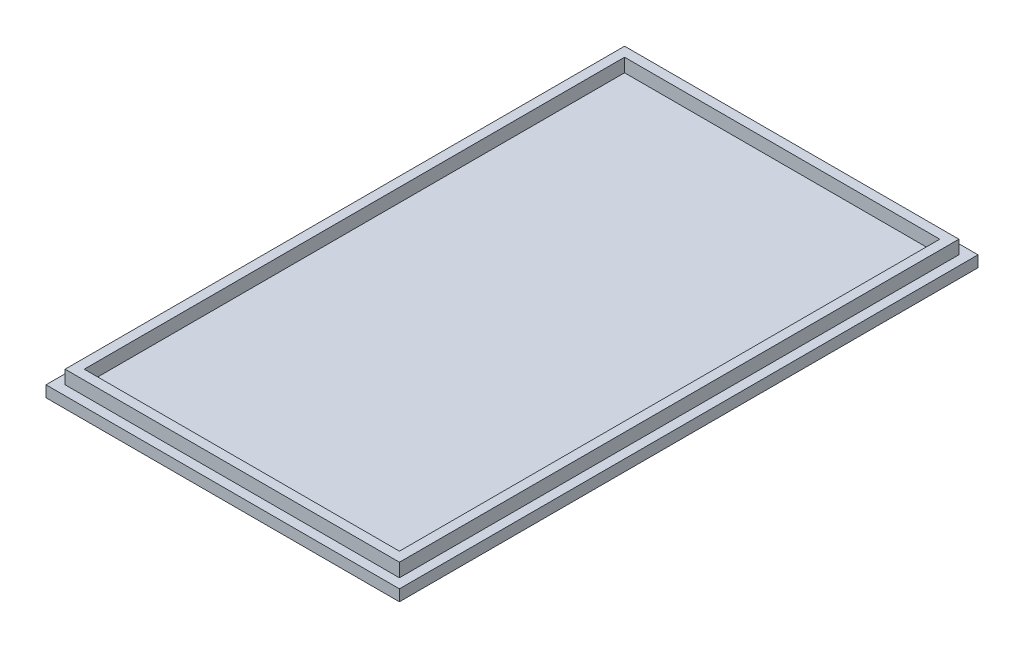
SolidWorks part; units mm, degrees
ref_plane "Front Plane" through (0, 0, 0) normal (0, 0, 1) x (1, 0, 0)
ref_plane "Top Plane" through (0, 0, 0) normal (0, 1, 0) x (1, 0, 0)
ref_plane "Right Plane" through (0, 0, 0) normal (1, 0, 0) x (0, 0, -1)
sketch "Sketch1" plane through (0, 0, 0) normal (0, 1, 0) x (1, 0, 0)
  line L5 (0, 0) -> (47.0912, 0)
  line L6 (0, 0) -> (0, -77.0912)
  line L7 (0, -77.0912) -> (47.0912, -77.0912)
  line L8 (47.0912, 0) -> (47.0912, -77.0912)
  point P5 (0, 0)
  point P7 (46.9516, -75.816)
  point P8 (0, 0)
  point P9 (0, 0)
  point P10 (0, 0)
extrude "Boss-Extrude1" add sketch "Sketch1" along normal blind 1.5
sketch "Sketch2" plane through (0, 1.5, 0) normal (0, 1, 0) x (1, 0, 0)
  line L3 (1.2728, -1.2728) -> (45.8184, -1.2728)
  line L4 (1.2728, -1.2728) -> (1.2728, -75.8184)
  line L5 (1.2728, -75.8184) -> (45.8184, -75.8184)
  line L6 (45.8184, -1.2728) -> (45.8184, -75.8184)
  line L7 (2.5456, -2.5456) -> (44.5456, -2.5456)
  line L8 (2.5456, -2.5456) -> (2.5456, -74.5456)
  line L9 (2.5456, -74.5456) -> (44.5456, -74.5456)
  line L10 (44.5456, -2.5456) -> (44.5456, -74.5456)
  point P2 (0, 0)
  point P3 (0, 0)
  point P12 (0, 0)
  point P14 (0, 0)
  point P15 (0, 0)
  point P16 (0, 0)
extrude "Boss-Extrude2" add sketch "Sketch2" along normal blind 1.8
